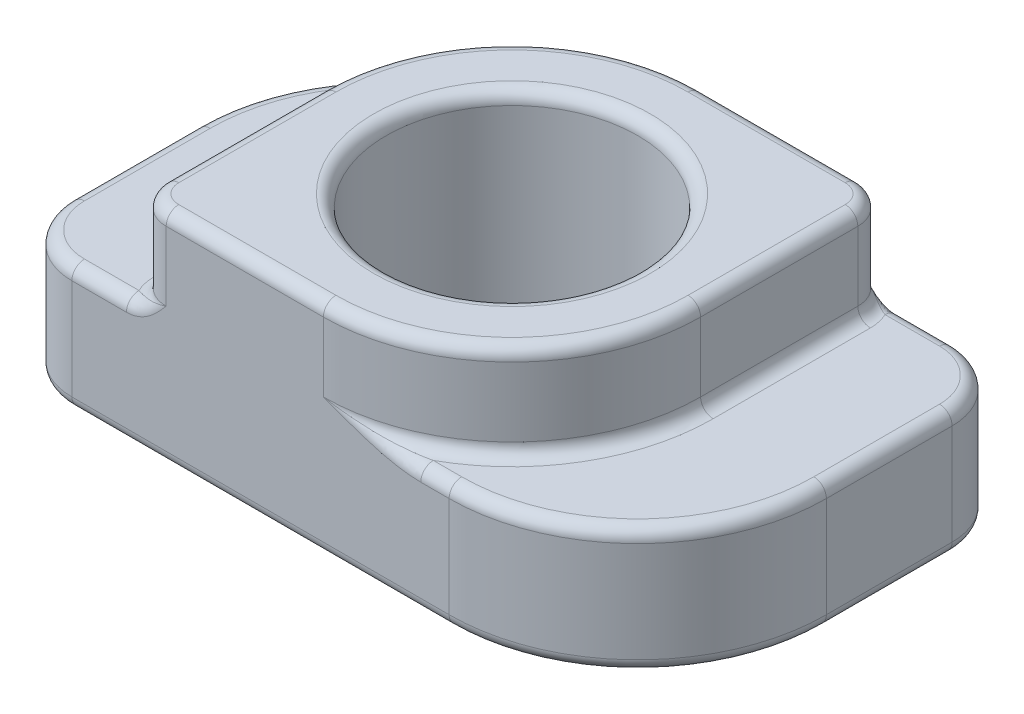
SolidWorks part; units mm, degrees
material "Galvanized Steel"
ref_plane "Plano frontal" through (0, 0, 0) normal (0, 0, 1) x (1, 0, 0)
ref_plane "Plano superior" through (0, 0, 0) normal (0, 1, 0) x (1, 0, 0)
ref_plane "Plano direito" through (0, 0, 0) normal (1, 0, 0) x (0, 0, -1)
sketch "Esboço1" plane through (0, 0, 0) normal (0, 1, 0) x (1, 0, 0)
  line L1 (-5, 3) -> (5, 3)
  line L2 (-5, 3) -> (-5, -3)
  line L3 (-5, -3) -> (5, -3)
  line L4 (5, 3) -> (5, -3)
  line L5 (-5, 3) -> (5, -3) construction
  line L6 (-5, -3) -> (5, 3) construction
  circle A0 centre (0, 0) radius 2
  point P0 (0, 0)
  dimension "D1" = 4
  dimension "D2" = 10
  dimension "D3" = 6
extrude "Ressalto-extrusão1" add sketch "Esboço1" along normal blind 2
sketch "Esboço2" plane through (0, 2, 0) normal (0, 1, 0) x (1, 0, 0)
  line L0 (-5, -3) -> (5, -3) construction
  line L3 (0, 3) -> (2.5, 3)
  line L4 (-3, 0) -> (-3, -2.5)
  line L5 (-2.5, -3) -> (0, -3)
  line L6 (3, 2.5) -> (3, 0)
  line L7 (-3, 3) -> (3, -3) construction
  line L8 (-3, -3) -> (3, 3) construction
  arc A0 (0, -3) -> (3, 0) centre (0, 0) ccw
  arc A1 (0, 3) -> (-3, 0) centre (0, 0) ccw
  arc A2 (2.5, 3) -> (3, 2.5) centre (2.5, 2.5) cw
  arc A3 (-3, -2.5) -> (-2.5, -3) centre (-2.5, -2.5) ccw
  point P0 (0, 0)
  dimension "D2" = 3
  dimension "D3" = 0.5
  dimension "D1" = 6
extrude "Ressalto-extrusão2" add sketch "Esboço2" along normal blind 1.5
sketch "Esboço3" plane through (0, 2, 0) normal (0, -1, 0) x (1, 0, 0)
  circle A0 centre (0, 0) radius 2
extrude "Corte-extrusão1" cut sketch "Esboço3" against normal blind 1.5
fillet "Filete1" radius 1 2 edges at (5, 1, -3) (-5, 1, 3)
fillet "Fillet1" radius 3 2 edges at (-5, 1, -3) (5, 1, 3)
fillet "Filete2" radius 0.2 34 edges at (2.1213, 2, 2.1213) (3, 2, -1.25) (2.8536, 2, -2.8536) (3.25, 2, -3) (4.7071, 2, -2.7071) (5, 2, -1) (1, 2, 3) (0, 0, 2) (4.7071, 0, -2.7071) (1, 0, -3) (-5, 0, 1) (-4.7071, 0, 2.7071) (-1, 0, 3) (5, 0, -1) (-2.1213, 2, -2.1213) (-3, 2, 1.25) (-2.8536, 2, 2.8536) (-3.25, 2, 3) (-4.7071, 2, 2.7071) (-5, 2, 1) (-1, 2, -3) (-1.25, 3.5, 3) (-2.8536, 3.5, 2.8536) (-3, 3.5, 1.25) (-2.1213, 3.5, -2.1213) (1.25, 3.5, -3) (2.8536, 3.5, -2.8536) (3, 3.5, -1.25) (2.1213, 3.5, 2.1213) (0, 3.5, -2) (4.1213, 0, 2.1213) (-4.1213, 0, -2.1213) (-4.1213, 2, -2.1213) (4.1213, 2, 2.1213)
